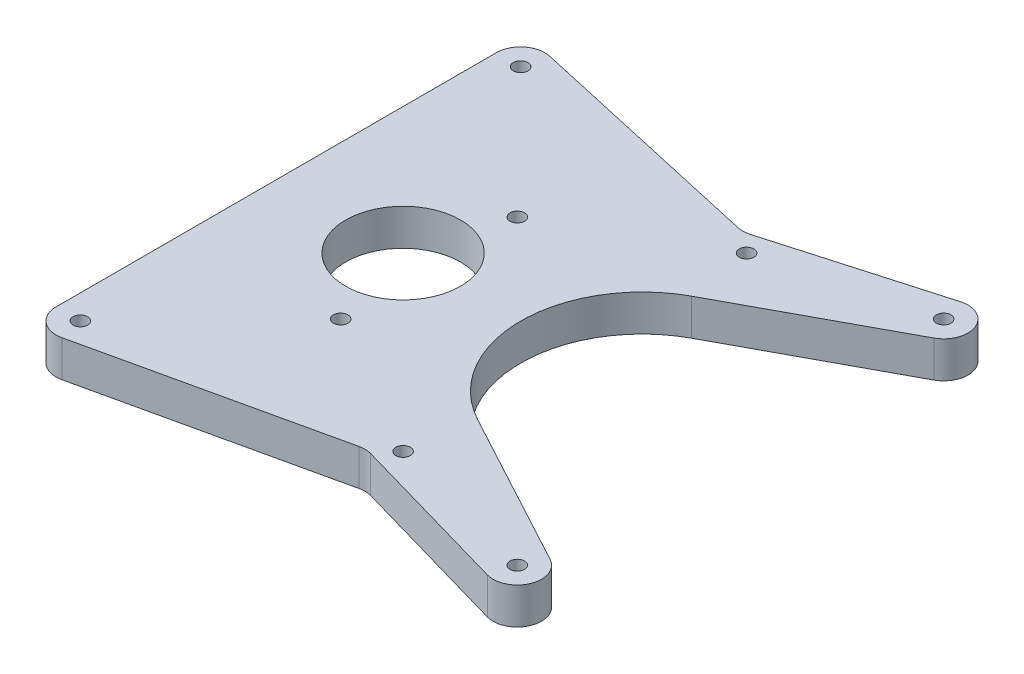
SolidWorks part; units mm, degrees
material "Alloy Steel"
ref_plane "Front Plane" through (0, 0, 0) normal (0, 0, 1) x (1, 0, 0)
ref_plane "Top Plane" through (0, 0, 0) normal (0, 1, 0) x (1, 0, 0)
ref_plane "Right Plane" through (0, 0, 0) normal (1, 0, 0) x (0, 0, -1)
sketch "Sketch2" plane through (0, 0, 0) normal (0, 1, 0) x (1, 0, 0)
  line L2 (62.5, 0) -> (25, 0) construction
  line L3 (25, 0) -> (0, 0) construction
  line L4 (62.5, 0) -> (179.6744, 0) construction
  line L5 (0, 0) -> (44.9013, 44.9013) construction
  line L6 (39.4146, 55.733) -> (62.5, 0) construction
  line L9 (62.5, 0) -> (85.5854, 55.733) construction
  line L10 (62.5, 0) -> (6.767, 23.0854) construction
  line L11 (0, 0) -> (-19.393, 0) construction
  line L12 (83.8387, 61.8381) -> (41.1613, 49.628)
  line L13 (38.0274, 49.5364) -> (-25.449, 63.7472)
  line L14 (0, 0) -> (-26.8363, 57.5505) construction
  line L15 (-25.449, -63.7472) -> (38.0274, -49.5364)
  line L16 (41.1613, -49.628) -> (83.8387, -61.8381)
  line L17 (0, 0) -> (44.9013, -44.9013) construction
  line L18 (-33.1863, 57.5505) -> (-33.1863, -57.5505)
  line L19 (0, 0) -> (-26.8363, -57.5505) construction
  line L21 (47.4315, 27.9464) -> (88.5991, 50.1438)
  line L22 (47.4315, -27.9464) -> (88.5991, -50.1438)
  arc A0 (47.4315, 27.9464) -> (47.4315, -27.9464) centre (62.5, 0) ccw
  circle A8 centre (6.767, 23.0854) radius 1.905
  circle A9 centre (85.5854, 55.733) radius 1.905
  circle A12 centre (85.5854, -55.733) radius 1.905
  circle A13 centre (6.767, -23.0854) radius 1.905
  circle A16 centre (0, 0) radius 25 construction
  circle A21 centre (85.5854, 55.733) radius 6.35
  circle A22 centre (85.5854, -55.733) radius 6.35
  circle A28 centre (0, 0) radius 15.0125
  circle A29 centre (-26.8363, 57.5505) radius 1.905
  circle A30 centre (44.9013, 44.9013) radius 1.905
  circle A33 centre (-26.8363, -57.5505) radius 1.905
  circle A34 centre (-26.8363, 57.5505) radius 6.35
  circle A35 centre (-26.8363, -57.5505) radius 6.35
  circle A37 centre (44.9013, -44.9013) radius 1.905
  circle A38 centre (39.4146, 55.733) radius 6.35
  circle A39 centre (39.4146, -55.733) radius 6.35
  dimension "D2" = 31.75
  dimension "D11" = 63.5
  dimension "D17" = 50
  dimension "D4" = 45
  dimension "D3" = 30.025
  dimension "D10" = 12.7
  dimension "D9" = 3.81
  dimension "D5" = 37.5
  dimension "D6" = 25
  dimension "D7" = 67.5
  dimension "D8" = 22.5
  dimension "D12" = 60.325
  dimension "D14" = 65
extrude "Boss-Extrude1" add sketch "Sketch2" along normal mid plane 9.525 contours A22 L22 A0 L21 A21 A16 | A13 | A22 A12 | A21 A9 | A8 | A34 A29 | A35 A33 region at (78.071, 0, -52.6742) region at (89.3003, 0, -60.6598) region at (-22.0201, 0, -61.4077) region at (90.8837, 0, 52.5704) region at (-26.8363, 0, 51.3801)
ref_axis "Turbine Axis" through (0, 5.2388, 0) along (0, -1, 0)
ref_axis "Pump Axis" through (62.5, 4.7625, 0) along (0, -1, 0)
sketch "Sketch3" plane through (0, 0, 0) normal (0, 1, 0) x (1, 0, 0)
  line L0 (0, 0) -> (-63.5, 0) construction
  line L1 (-63.5, -88.9) -> (114.3, -88.9)
  line L2 (-63.5, -88.9) -> (-63.5, 88.9)
  line L3 (-63.5, 88.9) -> (114.3, 88.9)
  line L4 (114.3, -88.9) -> (114.3, 88.9)
  point P5 (-63.5, 0)
  dimension "D1" = 177.8
  dimension "D2" = 63.5
